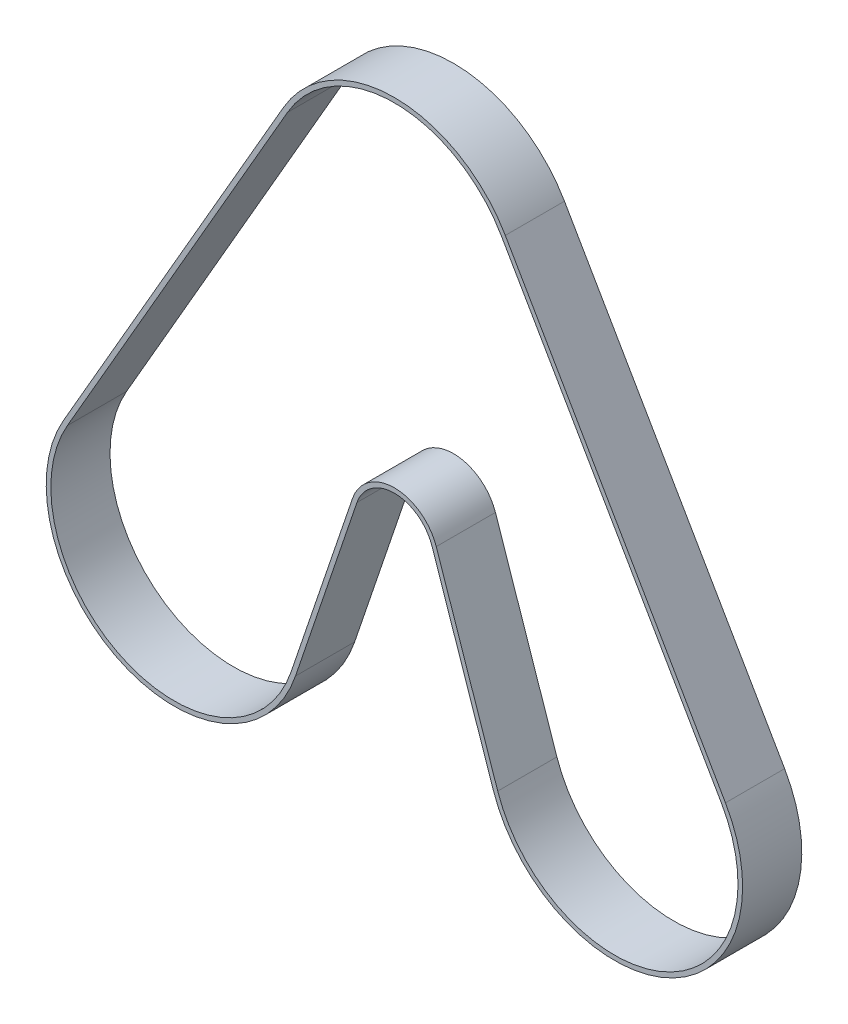
SolidWorks part; units mm, degrees
ref_plane "Plan de face" through (0, 0, 0) normal (0, 0, 1) x (1, 0, 0)
ref_plane "Plan de dessus" through (0, 0, 0) normal (0, 1, 0) x (1, 0, 0)
ref_plane "Plan de droite" through (0, 0, 0) normal (1, 0, 0) x (0, 0, -1)
sketch "Sketch1" plane through (0, 0, 0) normal (0, 0, 1) x (1, 0, 0)
  line L0 (-4.2895, 1.4565) -> (-10.9379, -18.1228)
  line L1 (4.2895, 1.4565) -> (10.9379, -18.1228)
  line L2 (35.5936, -6.95) -> (11.7779, 34.3)
  line L3 (-11.7779, 34.3) -> (-35.5936, -6.95)
  line L4 (0, 0) -> (0, 27.5) construction
  line L5 (0, 0) -> (23.8157, -13.75) construction
  line L6 (0, 0) -> (-23.8157, -13.75) construction
  circle A0 centre (0, 0) radius 27.5 construction
  arc A1 (-11.7779, 34.3) -> (11.7779, 34.3) centre (0, 27.5) cw
  arc A2 (-35.5936, -6.95) -> (-10.9379, -18.1228) centre (-23.8157, -13.75) ccw
  arc A3 (10.9379, -18.1228) -> (35.5936, -6.95) centre (23.8157, -13.75) ccw
  arc A4 (-4.2895, 1.4565) -> (4.2895, 1.4565) centre (0, 0) cw
  dimension "D1" = 13.6
  dimension "D2" = 4.53
  dimension "D3" = 55
  dimension "D4" = 120
  dimension "D5" = 120
extrude "Extrude-Thin1" add sketch "Sketch1" along normal mid plane 6.4 thin thin type mid plane wall 0.5
